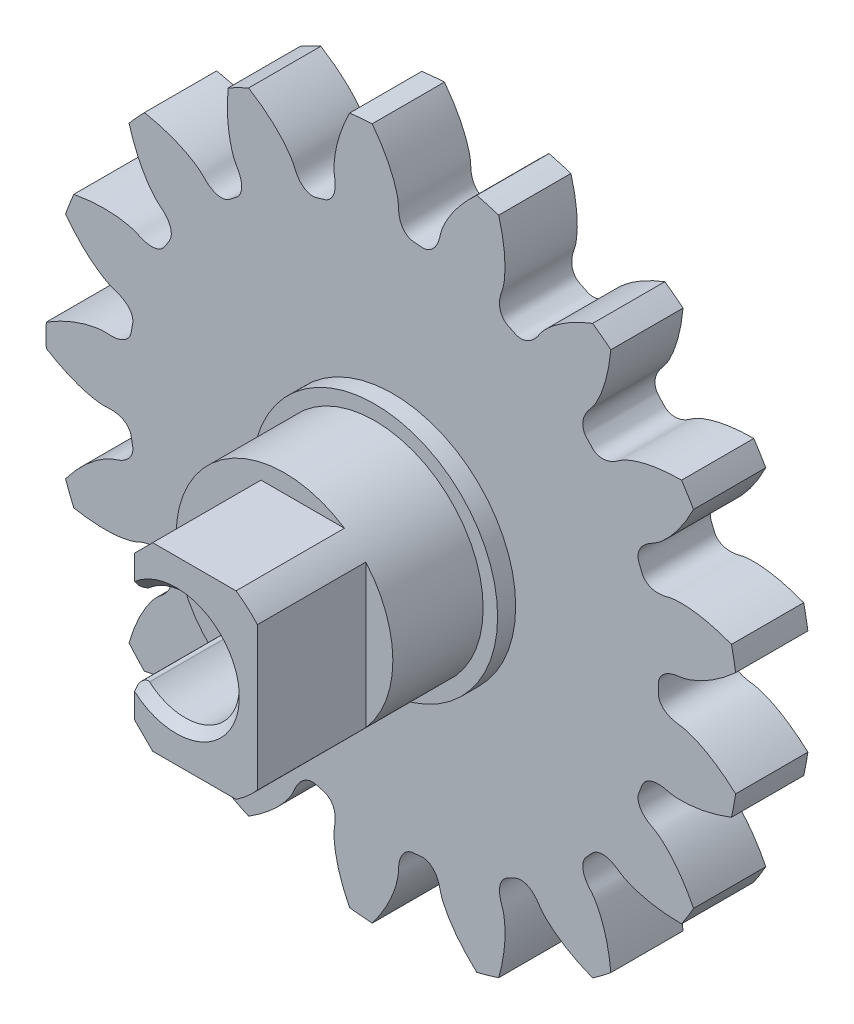
SolidWorks part; units mm, degrees
material "6061-T6 (SS)"
ref_plane "前视基准面" through (0, 0, 0) normal (0, 0, 1) x (1, 0, 0)
ref_plane "上视基准面" through (0, 0, 0) normal (0, 1, 0) x (1, 0, 0)
ref_plane "右视基准面" through (0, 0, 0) normal (1, 0, 0) x (0, 0, -1)
ref_axis "基准轴1" through (0, 0, 55) along (0, 0, -1)
sketch "旋转草图小直齿轮" plane through (0, 0, 0) normal (1, 0, 0) x (0, 0, -1)
  line L0 (-1, 0) -> (1, 0) construction
  line L1 (-2, 0) -> (-2, 19.2)
  line L2 (-2, 19.2) -> (2, 19.2)
  line L3 (2, 19.2) -> (2, 0)
  line L4 (2, 0) -> (-2, 0)
  line L5 (-2, 3) -> (2, 3)
  dimension "D1" = 19.2
  dimension "D2" = 2
  dimension "D3" = 2
  dimension "D4" = 3
revolve "小直齿轮" add sketch "旋转草图小直齿轮" angle 360 about L0 region at (0, 11.1, 0)
sketch "齿草图小直齿轮" plane through (0, 0, 0) normal (0, 0, 1) x (1, 0, 0)
  arc A0 (19.0763, 2.9953) -> (19.0763, -2.9953) centre (0, 0) cw
  spline S0 degree 3 poles (19.0763, -2.9953) (18.9059, -2.8359) (18.6497, -2.6111) (18.3026, -2.3373) (18.0577, -2.1573) (17.8221, -1.996) (17.5967, -1.8528) (17.3824, -1.7266) (17.1802, -1.6166) (16.9908, -1.5217) (16.815, -1.441) (16.6536, -1.3734) (16.5073, -1.3178) (16.3765, -1.2732) (16.262, -1.2383) (16.1641, -1.2121) (16.0834, -1.1934) (16.0201, -1.181) (15.9323, -1.1667) (15.8477, -1.1607) (15.7622, -1.148) (15.7118, -1.1398) (15.6622, -1.1305) (15.6136, -1.1202) (15.5658, -1.109) (15.5189, -1.0968) (15.4727, -1.0835) (15.4274, -1.0691) (15.3827, -1.0536) (15.3388, -1.0368) (15.2954, -1.0188) (15.2528, -0.9994) (15.2106, -0.9785) (15.1691, -0.9559) (15.128, -0.9315) (15.0874, -0.9051) (15.0474, -0.8765) (15.008, -0.8453) (14.9692, -0.8114) (14.9312, -0.7743) (14.8942, -0.7338) (14.8586, -0.6895) (14.8248, -0.6411) (14.7934, -0.5884) (14.7651, -0.5313) (14.7407, -0.4699) (14.7211, -0.4047) (14.7071, -0.3362) (14.6999, -0.2702) (14.697, -0.1579) (14.7024, 0) (14.697, 0.1579) (14.6999, 0.2702) (14.7071, 0.3362) (14.7211, 0.4047) (14.7407, 0.4699) (14.7651, 0.5313) (14.7934, 0.5884) (14.8248, 0.6411) (14.8586, 0.6895) (14.8942, 0.7338) (14.9312, 0.7743) (14.9692, 0.8114) (15.008, 0.8453) (15.0474, 0.8765) (15.0874, 0.9051) (15.128, 0.9315) (15.1691, 0.9559) (15.2106, 0.9785) (15.2528, 0.9994) (15.2954, 1.0188) (15.3388, 1.0368) (15.3827, 1.0536) (15.4274, 1.0691) (15.4727, 1.0835) (15.5189, 1.0968) (15.5658, 1.109) (15.6136, 1.1202) (15.6622, 1.1305) (15.7118, 1.1398) (15.7622, 1.148) (15.8477, 1.1607) (15.9323, 1.1667) (16.0201, 1.181) (16.0834, 1.1934) (16.1641, 1.2121) (16.262, 1.2383) (16.3765, 1.2732) (16.5073, 1.3178) (16.6536, 1.3734) (16.815, 1.441) (16.9908, 1.5217) (17.1802, 1.6166) (17.3824, 1.7266) (17.5967, 1.8528) (17.8221, 1.996) (18.0577, 2.1573) (18.3026, 2.3373) (18.6497, 2.6111) (18.9059, 2.8359) (19.0763, 2.9953) knots 0 0 0 0 0.062294 0.090982 0.118031 0.14344 0.16721 0.189341 0.209833 0.228685 0.245898 0.261471 0.275405 0.2877 0.298356 0.307372 0.314749 0.320487 0.324585 0.338492 0.34311 0.347658 0.352141 0.356564 0.36093 0.365246 0.369518 0.373752 0.377957 0.38214 0.386311 0.390481 0.394662 0.398867 0.403112 0.407412 0.411785 0.416252 0.420832 0.425548 0.43042 0.43547 0.440715 0.446168 0.451835 0.45771 0.463779 0.470011 0.476365 0.481469 0.5 0.518531 0.523635 0.529989 0.536221 0.54229 0.548165 0.553832 0.559285 0.56453 0.56958 0.574452 0.579168 0.583748 0.588215 0.592588 0.596888 0.601133 0.605338 0.609519 0.613689 0.61786 0.622043 0.626248 0.630482 0.634754 0.63907 0.643436 0.647859 0.652342 0.65689 0.661508 0.675415 0.679513 0.685251 0.692628 0.701644 0.7123 0.724595 0.738529 0.754102 0.771315 0.790167 0.810659 0.83279 0.85656 0.881969 0.909018 0.937706 1 1 1 1
extrude "齿拉伸切除小直齿轮" cut sketch "齿草图小直齿轮" against normal blind 3 and the other way blind 3
pattern_circular "齿形小直齿轮" count 17 over 360 about axis through (0, 0, 55) along (0, 0, -1) of "齿拉伸切除小直齿轮"
sketch "辅助草图小直齿轮" plane through (0, 0, 0) normal (0, 0, 1) x (1, 0, 0)
  circle A0 centre (0, 0) radius 17 construction
  circle A1 centre (0, 0) radius 15.9748 construction
  circle A2 centre (0, 0) radius 15.9766 construction
  circle A3 centre (0, 0) radius 19.2 construction
  circle A4 centre (0, 0) radius 14.7 construction
  dimension "PitchDiameter" = 34
  dimension "BaseDiameter" = 31.9495
  dimension "FormDiameter" = 31.9533
  dimension "MajorDiameter" = 38.4
  dimension "MinorDiameter" = 29.4
sketch "草图6" plane through (0, 0, 0) normal (1, 0, 0) x (0, 0, -1)
  line L0 (-17.5896, 0) -> (0, 0) construction
  line L1 (-2, -11.3522) -> (-2, 12.733) construction
  line L2 (-2, 3) -> (-2, 6.8)
  line L3 (-2, 6.8) -> (-3, 6.8)
  line L4 (-3, 6.8) -> (-3, 6)
  line L5 (-3, 6) -> (-8, 6)
  line L6 (-8, 6) -> (-8, 3)
  line L7 (-8, 3) -> (-2, 3)
  dimension "D1" = 6
  dimension "D2" = 13.6
  dimension "D3" = 12
  dimension "D4" = 1
  dimension "D5" = 5
  dimension "D6" = 2
revolve "旋转2" add sketch "草图6" angle 360 about L0
sketch "草图7" plane through (0, 0, 8) normal (0, 0, 1) x (1, 0, 0)
  line L0 (-10.4917, 0) -> (10.2009, 0) construction
  line L2 (-2.3, -5) -> (4.5, -5)
  line L3 (-2.3, -5) -> (-2.3, 5)
  line L4 (-2.3, 5) -> (4.5, 5)
  line L5 (4.5, -5) -> (4.5, 5)
  line L6 (-2.3, -5) -> (4.5, 5) construction
  line L7 (-2.3, 5) -> (4.5, -5) construction
  circle A0 centre (0, 0) radius 6 construction
  circle A1 centre (0, 0) radius 6
  circle A2 centre (0, 0) radius 3 construction
  circle A3 centre (0, 0) radius 3
  point P6 (1.1, 0)
  circle M4 centre (0, 0) radius 3
  circle M5 centre (0, 0) radius 6
  dimension "D1" = 4.5
  dimension "D2" = 10
  dimension "D3" = 6.8
extrude "凸台-拉伸1" add sketch "草图7" along normal blind 6 contours L5 L4 L3 L2 M5 M4 region at (-2.1791, -3.4631, 8)
chamfer "倒角1" distance 0.5 angle 45 1 edges at (3, 0, 14)
fillet "圆角1" radius 0.2 2 edges at (-2.3, 1.9261, 10.75) (-2.3, -1.9261, 10.75)
chamfer "倒角2" distance 1 angle 45 2 edges at (-2.3, 5, 11) (-2.3, -5, 11)
ref_plane "基准面1" through (0, 0, 0.5) normal (0, 0, -1) x (-1, 0, 0)
sketch "草图8" plane through (0, 0, 0.5) normal (0, 0, -1) x (-1, 0, 0)
  circle A0 centre (0, 0) radius 17 construction
  circle A1 centre (0, 0) radius 17 construction
move or copy body "实体-移动/复制1" [suppressed] bodies to move or copy 106
